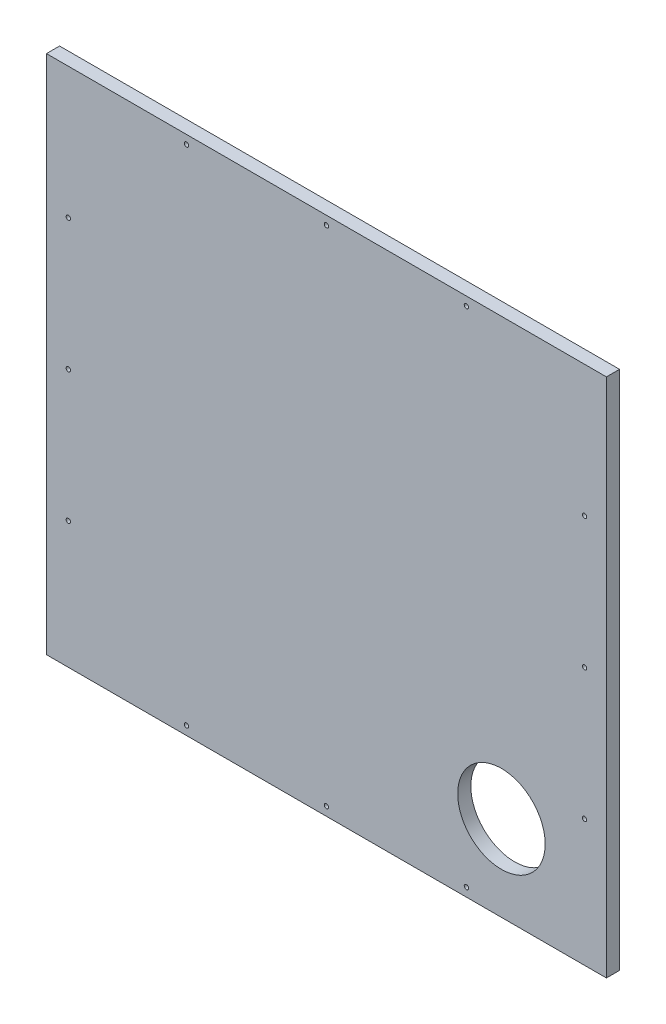
SolidWorks part; units mm, degrees
material "西洋杉"
ref_plane "正面" through (0, 0, 0) normal (0, 0, 1) x (1, 0, 0)
ref_plane "平面" through (0, 0, 0) normal (0, 1, 0) x (1, 0, 0)
ref_plane "右側面" through (0, 0, 0) normal (1, 0, 0) x (0, 0, -1)
sketch "ｽｹｯﾁ1" plane through (0, 0, 0) normal (0, 0, 1) x (1, 0, 0)
  line L1 (-320, 297.5) -> (320, 297.5)
  line L2 (-320, 297.5) -> (-320, -297.5)
  line L3 (-320, -297.5) -> (320, -297.5)
  line L4 (320, 297.5) -> (320, -297.5)
  line L5 (-320, 297.5) -> (320, -297.5) construction
  line L6 (-320, -297.5) -> (320, 297.5) construction
  point P0 (0, 0)
  dimension "D1" = 595
  dimension "D2" = 640
extrude "ﾎﾞｽ - 押し出し1" add sketch "ｽｹｯﾁ1" along normal blind 15
sketch "ｽｹｯﾁ2" plane through (0, 0, 15) normal (0, 0, 1) x (1, 0, 0)
  line L0 (-295, 297.5) -> (-295, -297.5) construction
  line L1 (320, 297.5) -> (-320, 297.5) construction
  line L2 (-320, -297.5) -> (320, -297.5) construction
  line L3 (-320, 297.5) -> (-320, -297.5) construction
  line L4 (-320, 287.5) -> (320, 287.5) construction
  line L5 (320, -297.5) -> (320, 297.5) construction
  circle A0 centre (-295, 147.5) radius 2.5
  circle A1 centre (-295, -2.5) radius 2.5
  circle A2 centre (-295, -152.5) radius 2.5
  circle A3 centre (-160, 287.5) radius 2.5
  circle A4 centre (0, 287.5) radius 2.5
  circle A5 centre (160, 287.5) radius 2.5
  dimension "D2" = 5
  dimension "D4" = 3
  dimension "D7" = 5
  dimension "D8" = 160
  dimension "D11" = 150
  dimension "D1" = 25
  dimension "D3" = 150
  dimension "D5" = 10
  dimension "D6" = 640
  dimension "D10" = 595
  dimension "D9" = 3
extrude "ｶｯﾄ - 押し出し1" cut sketch "ｽｹｯﾁ2" against normal through all contours A3 | A4 | A5
extrude "ｶｯﾄ - 押し出し2" cut sketch "ｽｹｯﾁ2<3>" against normal through all contours A0 | A1 | A2
sketch "ｽｹｯﾁ2<3>" plane through (0, 0, 15) normal (0, 0, 1) x (1, 0, 0) same geometry as "ｽｹｯﾁ2"
mirror "ﾐﾗｰ1" about plane through (0, 0, 0) normal (0, 1, 0) of "ｶｯﾄ - 押し出し1"
mirror "ﾐﾗｰ2" about plane through (0, 0, 0) normal (1, 0, 0) of "ｶｯﾄ - 押し出し2"
sketch "ｽｹｯﾁ3" plane through (0, 0, 15) normal (0, 0, 1) x (1, 0, 0)
  line L0 (200, 297.5) -> (200, -297.5) construction
  line L1 (320, 297.5) -> (-320, 297.5) construction
  line L2 (-320, -297.5) -> (320, -297.5) construction
  line L3 (-320, -200) -> (320, -200) construction
  line L4 (-320, 297.5) -> (-320, -297.5) construction
  line L5 (320, -297.5) -> (320, 297.5) construction
  circle A0 centre (200, -200) radius 50
  dimension "D3" = 100
  dimension "D1" = 200
  dimension "D2" = 200
extrude "ｶｯﾄ - 押し出し3" cut sketch "ｽｹｯﾁ3" against normal through all
